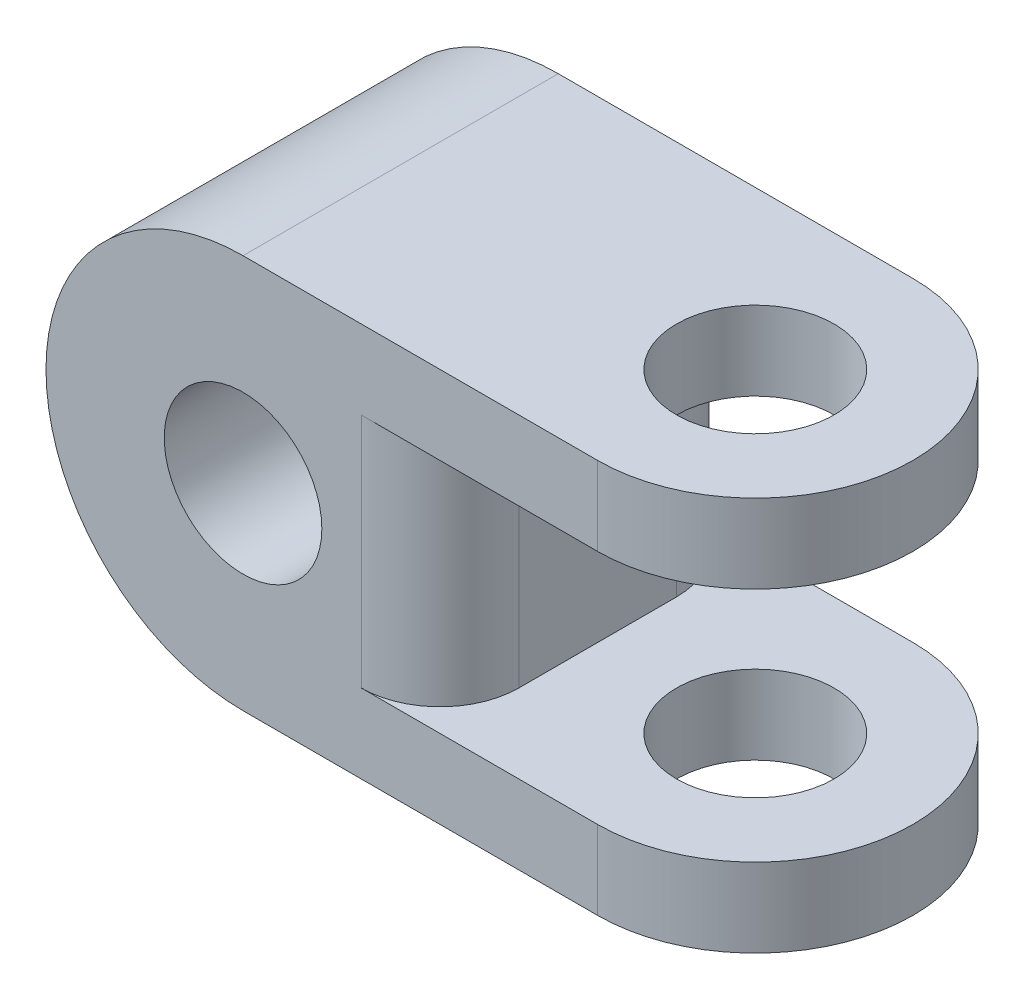
SolidWorks part; units mm, degrees
ref_plane "Front Plane" through (0, 0, 0) normal (0, 0, 1) x (1, 0, 0)
ref_plane "Top Plane" through (0, 0, 0) normal (0, 1, 0) x (1, 0, 0)
ref_plane "Right Plane" through (0, 0, 0) normal (1, 0, 0) x (0, 0, -1)
sketch "Sketch1" plane through (0, 0, 0) normal (0, 0, 1) x (1, 0, 0)
  line L0 (0, 0) -> (0, 10)
  line L1 (0, 10) -> (-65, 10)
  line L2 (-65, -40) -> (0, -40)
  line L3 (0, -40) -> (0, -30)
  line L4 (0, -30) -> (-40, -30)
  line L6 (-40, 0) -> (0, 0)
  line L7 (-40, 0) -> (-40, -30)
  arc A0 (-65, 10) -> (-65, -40) centre (-65, -15) ccw
  circle A1 centre (-65, -15) radius 10
  dimension "D1" = 25
  dimension "D2" = 20
  dimension "D3" = 30
  dimension "D4" = 10
  dimension "D5" = 10
  dimension "D6" = 65
  dimension "D7" = 25
extrude "Boss-Extrude1" add sketch "Sketch1" along normal mid plane 40
fillet "Fillet1" radius 10 2 edges at (-40, -15, -20) (-40, -15, 20)
sketch "Sketch2" plane through (0, 10, 0) normal (0, 1, 0) x (1, 0, 0)
  line L0 (-90, 20) -> (-90, -20) construction
  line L1 (0, 20) -> (-65, 20) construction
  circle A0 centre (-20, 0) radius 10
  dimension "D1" = 20
  dimension "D2" = 70
  dimension "D3" = 20
extrude "Cut-Extrude1" cut sketch "Sketch2" against normal up to next
extrude "Cut-Extrude2" cut sketch "Sketch2<2>" against normal up to next
sketch "Sketch2<2>" plane through (0, 10, 0) normal (0, 1, 0) x (1, 0, 0) same geometry as "Sketch2"
fillet "Fillet2" 2 edges at (0, -35, 20) (0, -35, -20) type full round first side face at (-31.875, -15, 20) second side face at (-31.875, -15, -20) middle face at (0, -35, 0)
fillet "Fillet3" 2 edges at (0, 5, 20) (0, 5, -20) type full round first side face at (-36.875, -15, 20) second side face at (-36.875, -15, -20) middle face at (0, 5, 0)
